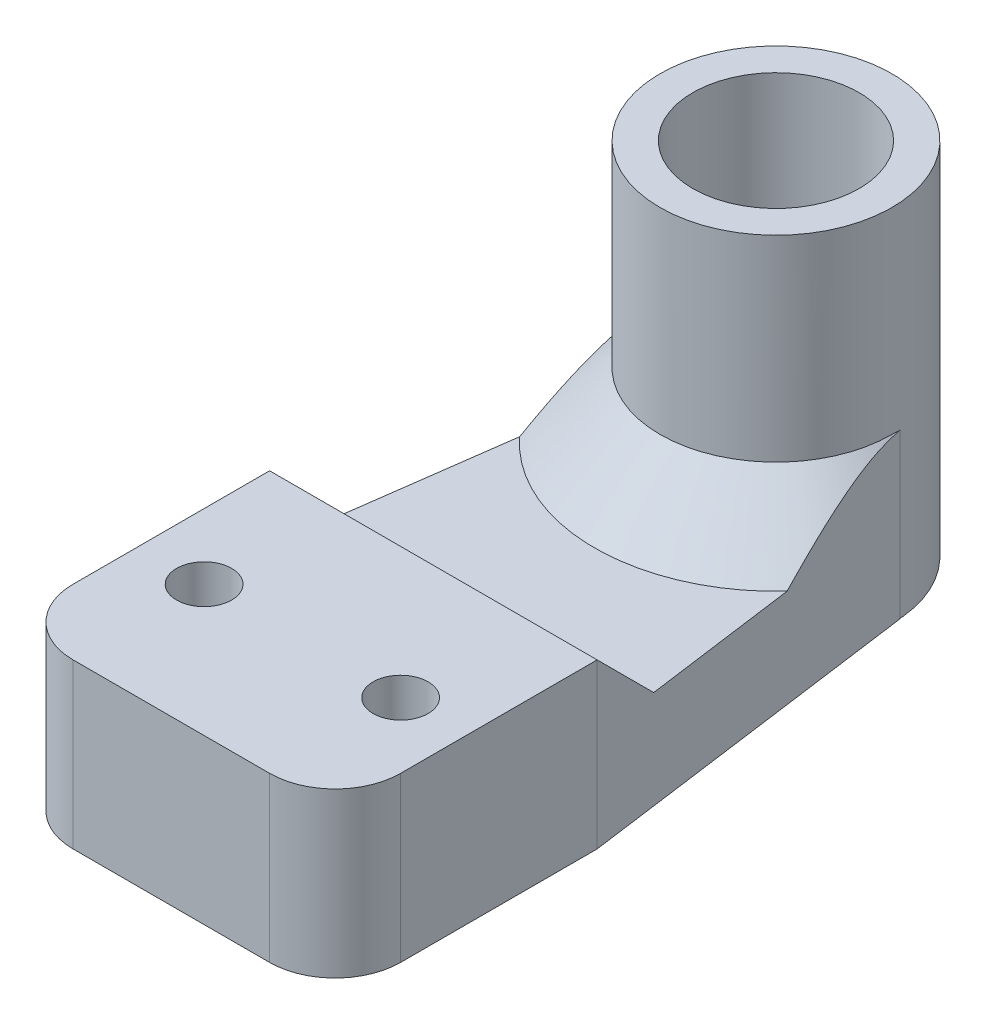
SolidWorks part; units mm, degrees
ref_plane "Front Plane" through (0, 0, 0) normal (0, 0, 1) x (1, 0, 0)
ref_plane "Top Plane" through (0, 0, 0) normal (0, 1, 0) x (1, 0, 0)
ref_plane "Right Plane" through (0, 0, 0) normal (1, 0, 0) x (0, 0, -1)
sketch "Sketch1" plane through (0, 0, 0) normal (0, 1, 0) x (1, 0, 0)
  line L0 (-12.5, 10) -> (-8.7688, 37.3464)
  line L1 (-12.5, -10) -> (12.5, -10)
  line L2 (-12.5, -10) -> (-12.5, 10)
  line L3 (-12.5, 10) -> (12.5, 10)
  line L4 (12.5, -10) -> (12.5, 10)
  line L5 (-12.5, -10) -> (12.5, 10) construction
  line L6 (-12.5, 10) -> (12.5, -10) construction
  line L7 (-8.85, 10) -> (8.85, 10)
  line L8 (-8.85, 10) -> (-8.85, 45)
  line L9 (-8.85, 45) -> (8.85, 45)
  line L10 (8.85, 10) -> (8.85, 45)
  line L11 (-8.85, 10) -> (8.85, 45) construction
  line L12 (-8.85, 45) -> (8.85, 10) construction
  line L13 (12.5, 10) -> (8.7688, 37.3464)
  circle A1 centre (0, 36.15) radius 8.85
  circle A2 centre (0, 36.15) radius 6.35
  circle A3 centre (-7.5, 0) radius 2.1
  circle A4 centre (7.5, 0) radius 2.1
  point P0 (0, 0)
  point P10 (0, 27.5)
  dimension "D3" = 12.7
  dimension "D4" = 2.5
  dimension "D5" = 4.2
  dimension "D1" = 35
  dimension "D2" = 20
  dimension "D6" = 15
  dimension "D7" = 25
  dimension "D8" = 7.5
extrude "Boss-Extrude1" add sketch "Sketch1" against normal blind 7.5 contours L1 L4 L3 L2 A4 A3 | A1 A2 | A1 L8 L3 L10 | A2 | L3 L8 L0 | L3 L13 L10 region at (0, 0, 0) region at (-10.0667, 0, -18.917) region at (0, 0, -19.7012) region at (-5.6549, 0, -42.6289) region at (10.0667, 0, -18.917) region at (0, 0, -36.15)
extrude "Boss-Extrude2" add sketch "Sketch1<3>" along normal blind 5 contours L1 L4 L3 L2 A4 A3 region at (0, 0, 0)
sketch "Sketch1<3>" plane through (0, 0, 0) normal (0, 1, 0) x (1, 0, 0) same geometry as "Sketch1"
extrude "Boss-Extrude3" add sketch "Sketch1<4>" along normal blind 20 contours A1 A2 region at (-5.6549, 0, -42.6289)
sketch "Sketch1<4>" plane through (0, 0, 0) normal (0, 1, 0) x (1, 0, 0) same geometry as "Sketch1"
chamfer "Chamfer1" distance 5 angle 45 2 edges at (0, 0, -10) (0, 0, -27.3)
fillet "Fillet1" radius 5 2 edges at (12.5, -1.25, 10) (-12.5, -1.25, 10)
equation "\"m3 hole\"= 3.2"
equation "\"m4 hole\"= 4.2"
equation "\"m5 hole\"= 5.2"
equation "\"m6 hole\"= 6.2"
equation "\"m8 hole\"= 8.2"
equation "\"m3 tapped\"= 2.5"
equation "\"m4 tapped\"= 3.3"
equation "\"m5 tapped\"= 4.2"
equation "\"m6 tapped\"= 5"
equation "\"m8 tapped\"= 6.8"
